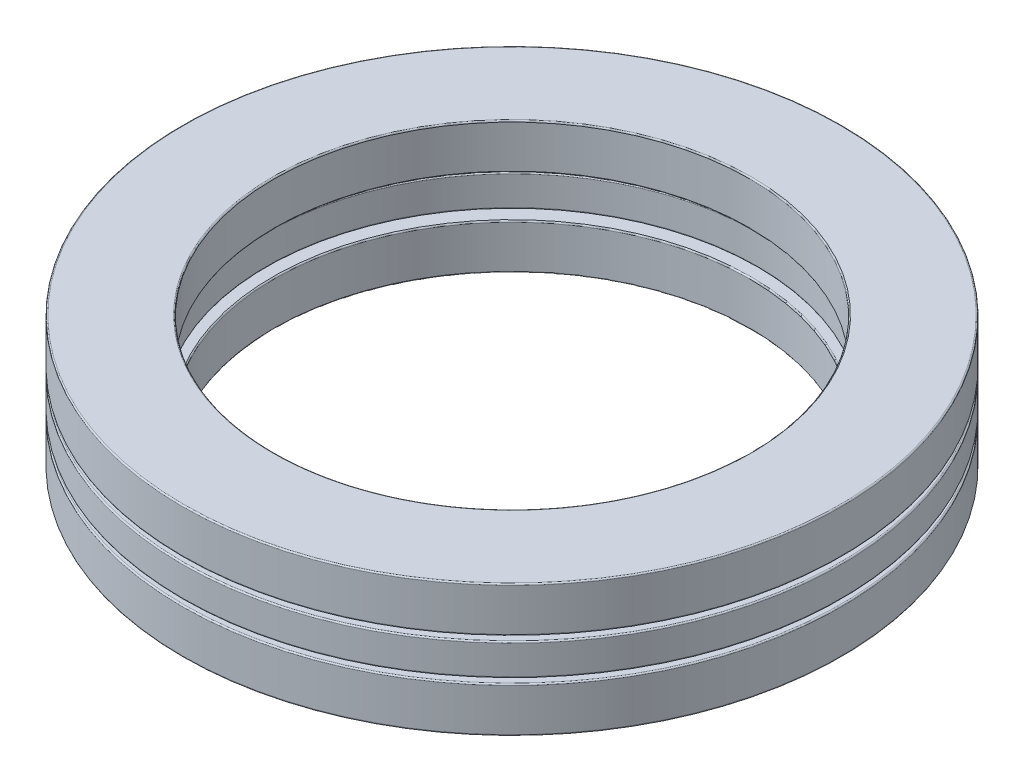
SolidWorks part; units mm, degrees
ref_plane "Front Plane" through (0, 0, 0) normal (0, 0, 1) x (1, 0, 0)
ref_plane "Top Plane" through (0, 0, 0) normal (0, 1, 0) x (1, 0, 0)
ref_plane "Right Plane" through (0, 0, 0) normal (1, 0, 0) x (0, 0, -1)
sketch "Sketch1" plane through (0, 0, 0) normal (0, 0, 1) x (1, 0, 0)
  line L0 (-45, 1.9825) -> (-45, -1.9825)
  line L1 (-44.82, -2.1625) -> (-33.68, -2.1625)
  line L2 (-33.5, -1.9825) -> (-33.5, 1.9825)
  line L3 (-33.68, 2.1625) -> (-44.82, 2.1625)
  line L4 (0, -9) -> (0, 9) construction
  line L5 (-45, 8.82) -> (-45, 3.0225)
  line L6 (-44.82, 2.8425) -> (-32.68, 2.8425)
  line L7 (-32.5, 3.0225) -> (-32.5, 8.82)
  line L8 (-32.68, 9) -> (-44.82, 9)
  line L9 (-39.25, 3.5225) -> (-39.25, 2.1625) construction
  arc A0 (-45, 1.9825) -> (-44.82, 2.1625) centre (-44.82, 1.9825) cw
  arc A1 (-33.68, 2.1625) -> (-33.5, 1.9825) centre (-33.68, 1.9825) cw
  arc A2 (-33.5, -1.9825) -> (-33.68, -2.1625) centre (-33.68, -1.9825) cw
  arc A3 (-44.82, -2.1625) -> (-45, -1.9825) centre (-44.82, -1.9825) cw
  circle A4 centre (-39.25, 0) radius 3.46
  arc A5 (-32.68, 2.8425) -> (-32.5, 3.0225) centre (-32.68, 3.0225) ccw
  arc A6 (-32.5, 8.82) -> (-32.68, 9) centre (-32.68, 8.82) ccw
  arc A7 (-44.82, 9) -> (-45, 8.82) centre (-44.82, 8.82) ccw
  arc A8 (-45, 3.0225) -> (-44.82, 2.8425) centre (-44.82, 3.0225) ccw
  circle A9 centre (-39.25, 0) radius 3.5225 construction
  point P15 (-33.5, 0)
  point P24 (-39.25, 2.8425)
  dimension "D1" = 0.18
  dimension "Thickness" = 18
  dimension "D2" = 4.325
  dimension "D3" = 0.0625
  dimension "Washer ID" = 65
sketch "Sketch2" plane through (0, 0, 0) normal (0, 0, 1) x (1, 0, 0)
  line L0 (-33.5, -1.9825) -> (-33.5, 1.9825) construction
  line L1 (-44.82, -2.1625) -> (-33.68, -2.1625) construction
  line L2 (-45, 1.9825) -> (-45, -1.9825) construction
  line L3 (-33.68, 2.1625) -> (-44.82, 2.1625) construction
  line L4 (-33.5, -1.9825) -> (-33.5, 1.9825)
  line L5 (-44.82, -2.1625) -> (-33.68, -2.1625)
  line L6 (-45, 1.9825) -> (-45, -1.9825)
  line L7 (-33.68, 2.1625) -> (-44.82, 2.1625)
  arc A0 (-33.5, 1.9825) -> (-33.68, 2.1625) centre (-33.68, 1.9825) ccw construction
  arc A1 (-33.68, -2.1625) -> (-33.5, -1.9825) centre (-33.68, -1.9825) ccw construction
  arc A2 (-45, -1.9825) -> (-44.82, -2.1625) centre (-44.82, -1.9825) ccw construction
  arc A3 (-44.82, 2.1625) -> (-45, 1.9825) centre (-44.82, 1.9825) ccw construction
  arc A4 (-33.5, 1.9825) -> (-33.68, 2.1625) centre (-33.68, 1.9825) ccw
  arc A5 (-33.68, -2.1625) -> (-33.5, -1.9825) centre (-33.68, -1.9825) ccw
  arc A6 (-45, -1.9825) -> (-44.82, -2.1625) centre (-44.82, -1.9825) ccw
  arc A7 (-44.82, 2.1625) -> (-45, 1.9825) centre (-44.82, 1.9825) ccw
revolve "Revolve2" add sketch "Sketch2" angle 360 about L4
sketch "Sketch4" plane through (0, 0, 0) normal (0, 0, 1) x (1, 0, 0)
  line L0 (-9, 0) -> (9, 0) construction
  line L1 (0, -9) -> (0, 9) construction
  line L2 (-32.5, 3.0225) -> (-32.5, 8.82) construction
  line L3 (-45, 8.82) -> (-45, 3.0225) construction
  line L5 (-44.82, 2.8425) -> (-41.3304, 2.8425)
  line L6 (-45, 8.82) -> (-45, 3.0225)
  line L10 (-41.3304, 2.8425) -> (-37.1696, 2.8425) construction
  line L11 (-39.25, 3.5225) -> (-39.25, 2.8425) construction
  line L12 (-39.25, 3.5225) -> (-39.25, 2.8425) construction
  line L13 (-39.25, 3.5225) -> (-39.25, 2.1625) construction
  line L14 (-32.5, 3.0225) -> (-32.5, 8.82)
  line L15 (-32.68, 9) -> (-44.82, 9) construction
  line L16 (-32.68, 9) -> (-44.82, 9)
  line L17 (-37.1696, 2.8425) -> (-32.68, 2.8425)
  arc A0 (-37.1696, 2.8425) -> (-41.3304, 2.8425) centre (-39.25, 0) ccw
  arc A1 (-32.68, 2.8425) -> (-32.5, 3.0225) centre (-32.68, 3.0225) ccw construction
  circle A2 centre (-39.25, 0) radius 3.5225 construction
  arc A3 (-32.68, 2.8425) -> (-32.5, 3.0225) centre (-32.68, 3.0225) ccw
  arc A4 (-32.5, 8.82) -> (-32.68, 9) centre (-32.68, 8.82) ccw construction
  arc A8 (-45, 3.0225) -> (-44.82, 2.8425) centre (-44.82, 3.0225) ccw
  arc A10 (-32.5, 8.82) -> (-32.68, 9) centre (-32.68, 8.82) ccw
  arc A11 (-44.82, 9) -> (-45, 8.82) centre (-44.82, 8.82) ccw construction
  arc A12 (-44.82, 9) -> (-45, 8.82) centre (-44.82, 8.82) ccw
revolve "Revolve3" add sketch "Sketch4" angle 360 about L4
mirror "Mirror1" about plane through (0, 0, 0) normal (0, 1, 0) of bodies 107
sketch "Sketch3" plane through (0, 0, 0) normal (0, 0, 1) x (1, 0, 0)
  line L0 (-39.25, 3.5225) -> (-39.25, -3.5225)
  arc A0 (-39.25, 3.5225) -> (-39.25, -3.5225) centre (-39.25, 0) ccw
revolve "Cut-Revolve1" cut sketch "Sketch3" angle 360 about L0
sketch "Sketch5" plane through (0, 0, 0) normal (0, 0, 1) x (1, 0, 0)
  line L0 (-39.25, 3.46) -> (-39.25, -3.46)
  arc A0 (-39.25, 3.46) -> (-39.25, -3.46) centre (-39.25, 0) ccw
  circle A1 centre (-39.25, 0) radius 3.46 construction
revolve "Revolve4" add sketch "Sketch5" angle 360 about L0
pattern_circular "CirPattern2" count 33 over 360 about axis through (0, -9, 0) along (0, 1, 0) of "Cut-Revolve1" reverse direction yes
pattern_circular "CirPattern3" count 33 over 360 about axis through (0, -9, 0) along (0, 1, 0) reverse direction yes of bodies 109
sketch "Sketch6" plane through (0, 0, 0) normal (0, 1, 0) x (1, 0, 0)
  circle A0 centre (0, 0) radius 45
  circle A1 centre (0, 0) radius 32.5
  dimension "Washer ID" = 65
  dimension "OD" = 90
ref_plane "Contact Plane 1" through (0, 9, 0) normal (0, 1, 0) x (1, 0, 0)
ref_plane "Contact Plane 2" through (0, -9, 0) normal (0, -1, 0) x (-1, 0, 0)
ref_axis "Center Axis 1" through (0, 1.9825, 0) along (0, -1, 0)
equation "\"D2@Sketch1\"=\"Ball Diameter@Sketch1\"*.625"
equation "\"D1@Sketch1\"=\"Thickness@Sketch1\"*.01"
equation "\"D1@CirPattern3\" = \"Balls@CirPattern2\""
